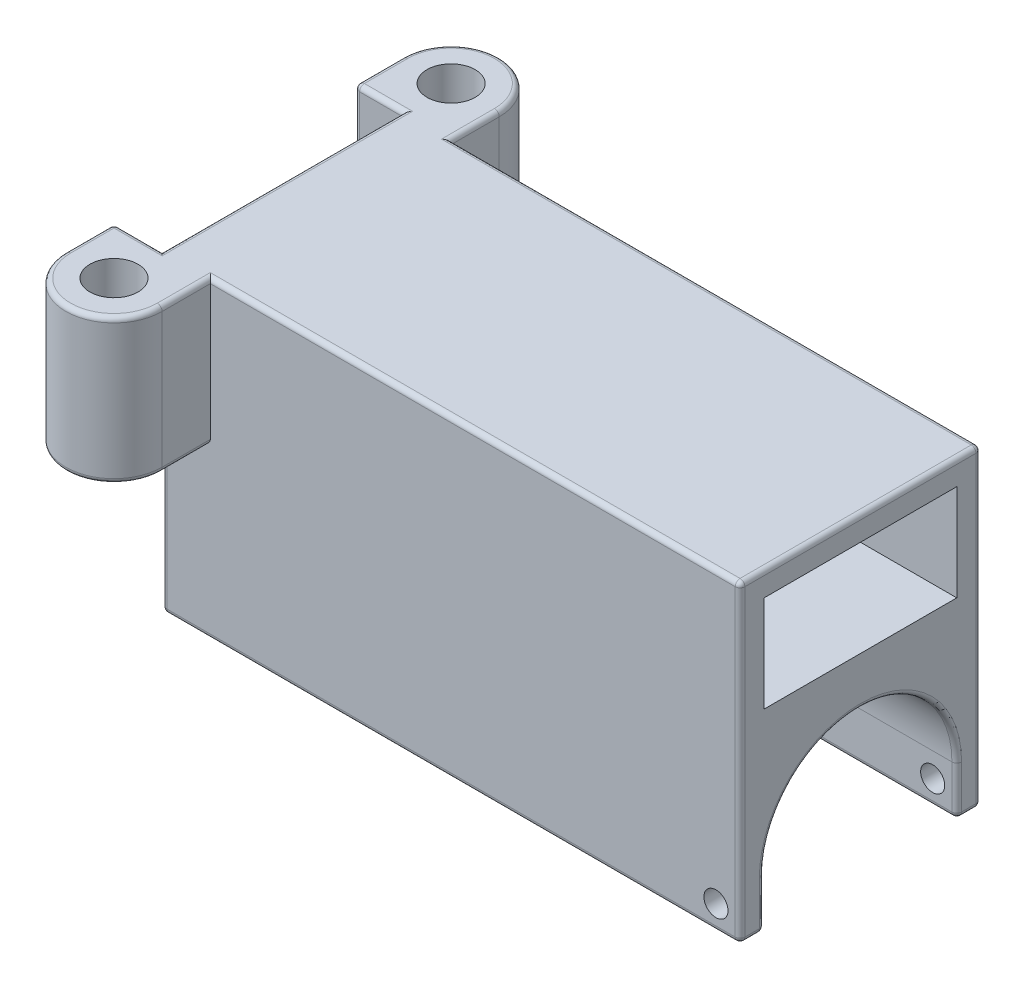
SolidWorks part; units mm, degrees
material "Aleación 2024"
ref_plane "Alzado" through (0, 0, 0) normal (0, 0, 1) x (1, 0, 0)
ref_plane "Planta" through (0, 0, 0) normal (0, 1, 0) x (1, 0, 0)
ref_plane "Vista lateral" through (0, 0, 0) normal (1, 0, 0) x (0, 0, -1)
sketch "Croquis1" plane through (0, 0, 0) normal (0, 1, 0) x (1, 0, 0)
  line L1 (-60, -25) -> (60, -25)
  line L2 (-60, -25) -> (-60, 25)
  line L3 (-60, 25) -> (60, 25)
  line L4 (60, -25) -> (60, 25)
  line L5 (-60, -25) -> (60, 25) construction
  line L6 (-60, 25) -> (60, -25) construction
  point P0 (0, 0)
  dimension "D1" = 120
  dimension "D2" = 50
extrude "Saliente-Extruir2" add sketch "Croquis1" along normal blind 30 contours L1 L4 L3 L2
sketch "Croquis8" plane through (0, 0, 25) normal (0, 0, 1) x (1, 0, 0)
  line L1 (-70, 30) -> (-50, 30)
  line L2 (-70, 30) -> (-70, 0)
  line L3 (-70, 0) -> (-50, 0)
  line L4 (-50, 30) -> (-50, 0)
  dimension "D1" = 20
extrude "Saliente-Extruir3" add sketch "Croquis8" along normal blind 20
mirror "Simetría4" about plane through (0, 0, 0) normal (0, 0, 1) of "Saliente-Extruir3"
sketch "Croquis9" plane through (0, 30, 0) normal (0, 1, 0) x (1, 0, 0)
  circle A0 centre (-60, 35) radius 5
  circle A1 centre (-60, -35) radius 5
  dimension "D1" = 10
  dimension "D2" = 10
extrude "Cortar-Extruir3" cut sketch "Croquis9" against normal up to next
sketch "Croquis11" plane through (0, 30, 0) normal (0, 1, 0) x (1, 0, 0)
  line L0 (-70, -35) -> (-70, -45)
  line L1 (-70, -45) -> (-50, -45)
  line L2 (-50, -45) -> (-50, -35)
  line L3 (-50, 35) -> (-50, 45)
  line L4 (-50, 45) -> (-70, 45)
  line L6 (-70, 45) -> (-70, 35)
  arc A0 (-50, 35) -> (-70, 35) centre (-60, 35) ccw
  arc A1 (-70, -35) -> (-50, -35) centre (-60, -35) ccw
  line M5 (-50, 25) -> (-50, 45)
  line M6 (-50, 45) -> (-70, 45)
  line M7 (-60, 25) -> (-60, -25)
  line M8 (-70, -45) -> (-50, -45)
  line M9 (-50, -45) -> (-50, -25)
extrude "Cortar-Extruir5" cut sketch "Croquis11" against normal up to next contours A1 L1 M9 | A1 M7 M8 | A0 M5 M6 | A0 L4 M7 region at (-67.7663, 30, 42.7663) region at (-52.2337, 30, 42.7663) region at (-52.2337, 30, -42.7663) region at (-67.7663, 30, -42.7663)
sketch "Croquis12" plane through (60, 0, 0) normal (1, 0, 0) x (0, 0, -1)
  line L1 (-20, 25) -> (20, 25)
  line L2 (-20, 25) -> (-20, 5)
  line L3 (-20, 5) -> (20, 5)
  line L4 (20, 25) -> (20, 5)
  line L5 (-20, 25) -> (20, 5) construction
  line L6 (-20, 5) -> (20, 25) construction
  point P0 (0, 15)
  dimension "D1" = 40
  dimension "D2" = 20
extrude "Cortar-Extruir6" cut sketch "Croquis12" against normal up to surface (110 mm away) up to face at (-50, 15, 30)
sketch "Croquis13" plane through (60, 0, 0) normal (1, 0, 0) x (0, 0, -1)
  line L0 (0, 0) -> (0, -25) construction
  line L1 (-25, 0) -> (25, 0)
  line L2 (-25, 0) -> (-25, -35)
  line L4 (25, 0) -> (25, -35)
  line L6 (-25, -35) -> (-20, -35)
  line L7 (-20, -35) -> (-20, -25)
  line L8 (25, -35) -> (20, -35)
  line L9 (20, -35) -> (20, -25)
  arc A0 (20, -25) -> (-20, -25) centre (0, -25) ccw
  dimension "D2" = 20
  dimension "D3" = 35
  dimension "D4" = 35
  dimension "D1" = 25
extrude "Saliente-Extruir7" add sketch "Croquis13" against normal blind 120
sketch "Croquis14" plane through (0, 0, -25) normal (0, 0, -1) x (-1, 0, 0)
  line L0 (-60, -35) -> (-55, -35) construction
  line L1 (60, -35) -> (-60, -35) construction
  line L2 (-55, -35) -> (-55, -30) construction
  circle A0 centre (-55, -30) radius 2.5
  dimension "D3" = 5
  dimension "D1" = 5
  dimension "D2" = 5
extrude "Cortar-Extruir7" cut sketch "Croquis14" against normal up to surface (50 mm away) up to face at (-16.6667, -1.6667, 25)
sketch "Croquis15" plane through (-60, 0, 0) normal (-1, 0, 0) x (0, 0, 1)
  line L6 (-25, 0) -> (25, 0)
  line L8 (-25, 0) -> (-25, 30)
  line L9 (-25, 30) -> (25, 30)
  line L10 (25, 0) -> (25, 30)
  line L14 (-22, 3) -> (-22, 27)
  line L15 (-22, 27) -> (22, 27)
  line L16 (22, 3) -> (22, 27)
  line L17 (-22, 3) -> (22, 3)
  dimension "D1" = 3
extrude "Cortar-Extruir8" cut sketch "Croquis15" against normal blind 20 contours L14 L15 L16 L17
fillet "Redondeo2" radius 1 46 edges at (-60, -30, 20) (-60, -30, -20) (-50, 30, -30) (-60, 30, -45) (-50, 30, 30) (-60, 30, 45) (60, 30, 0) (60, -2.5, -25) (60, -35, -22.5) (60, -30, -20) (60, -5, 0) (60, -30, 20) (60, -35, 22.5) (60, -2.5, 25) (-60, -35, 22.5) (-60, -35, -22.5) (0, -35, -20) (0, -35, 20) (-60, -5, 0) (-60, -17.5, 25) (0, -35, 25) (-60, -17.5, -25) (0, -35, -25) (-40, 25, 0) (-40, 15, -20) (-40, 15, 20) (-40, 5, 0) (-70, 15, -25) (-70, 15, 25) (-70, 30, -30) (-65, 30, -25) (-70, 30, 30) (-65, 30, 25) (-60, 30, 0) (5, 30, 25) (5, 30, -25) (-50, 0, -30) (-70, 0, -30) (-70, 0, 30) (-50, 0, 30) (-60, 0, -45) (-60, 0, 45) (-60, 15, 22) (-60, 3, 0) (-60, 15, -22) (-60, 27, 0)
